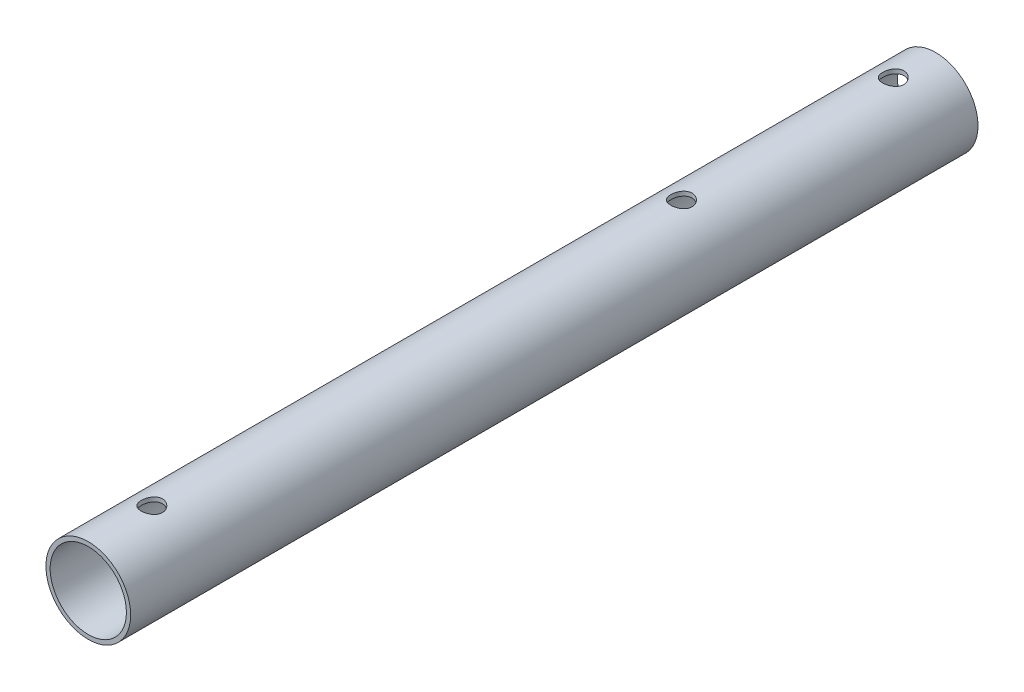
SolidWorks part; units mm, degrees
ref_plane "Ön Düzlem" through (0, 0, 0) normal (0, 0, 1) x (1, 0, 0)
ref_plane "Üst Düzlem" through (0, 0, 0) normal (0, 1, 0) x (1, 0, 0)
ref_plane "Sağ Düzlem" through (0, 0, 0) normal (1, 0, 0) x (0, 0, -1)
sketch "Çizim1" plane through (0, 0, 0) normal (0, 0, 1) x (1, 0, 0)
  circle A0 centre (0, 0) radius 10
  circle A1 centre (0, 0) radius 9
  dimension "D1" = 20
  dimension "D2" = 18
extrude "Yükseklik-Ekstrüzyon1" add sketch "Çizim1" along normal blind 200 contours A0 | A1
sketch "Çizim2" plane through (0, 0, 0) normal (0, 1, 0) x (1, 0, 0)
  line L0 (10, 0) -> (-10, 0) construction
  circle A0 centre (0, -10) radius 2.5
  circle A1 centre (0, -60) radius 2.5
  point P4 (0, -16.095)
  dimension "D1" = 5
  dimension "D2" = 5
  dimension "D3" = 50
  dimension "D4" = 10
extrude "Kes-Ekstrüzyon1" cut sketch "Çizim2" along normal blind 200 and the other way blind 200
sketch "Çizim3" plane through (0, 0, 0) normal (0, 1, 0) x (1, 0, 0)
  circle A0 centre (0, -185) radius 2.5
  dimension "D2" = 5
  dimension "D1" = 185
extrude "Kes-Ekstrüzyon2" cut sketch "Çizim3" against normal blind 200 and the other way blind 200
